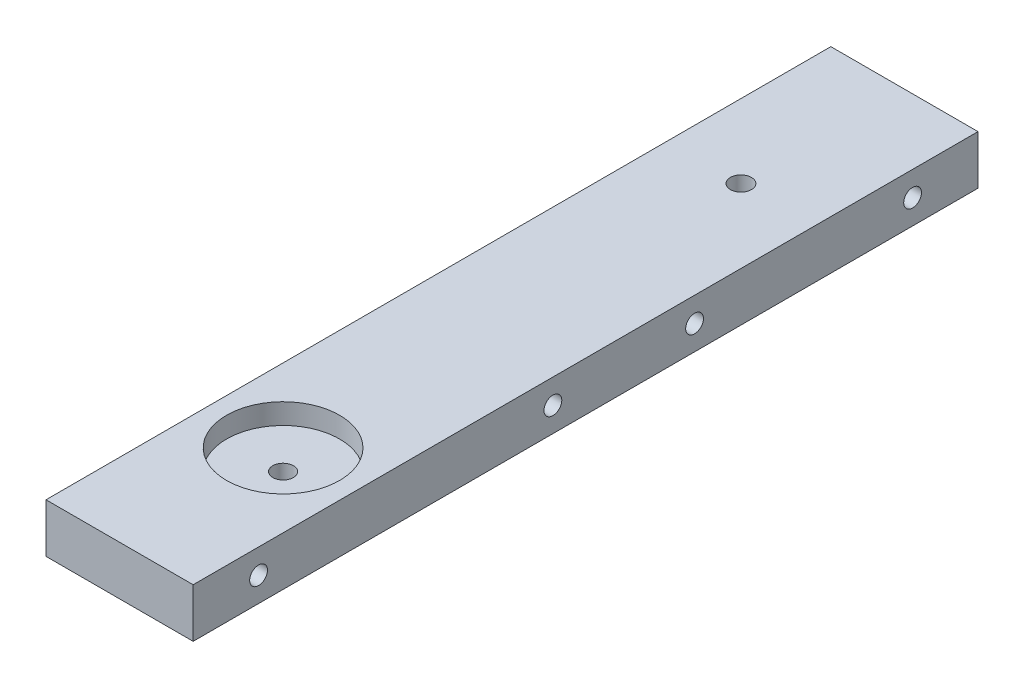
SolidWorks part; units mm, degrees
ref_plane "Front Plane" through (0, 0, 0) normal (0, 0, 1) x (1, 0, 0)
ref_plane "Top Plane" through (0, 0, 0) normal (0, 1, 0) x (1, 0, 0)
ref_plane "Right Plane" through (0, 0, 0) normal (1, 0, 0) x (0, 0, -1)
sketch "Sketch2" plane through (0, 0, 0) normal (0, 1, 0) x (1, 0, 0)
  line L0 (0, 0) -> (0, 152.4)
  line L1 (0, 152.4) -> (28.575, 152.4)
  line L2 (28.575, 152.4) -> (28.575, 0)
  line L3 (28.575, 0) -> (0, 0)
  dimension "D1" = 152.4
  dimension "D2" = 28.575
extrude "Boss-Extrude1" add sketch "Sketch2" along normal blind 9.525
sketch "Sketch3" plane through (0, 0, 0) normal (-1, 0, 0) x (0, 0, 1)
  line L3 (-152.4, 9.525) -> (0, 9.525) construction
  line L4 (-152.4, 9.525) -> (-152.4, 0) construction
  point P6 (-139.7, 4.7625)
  point P14 (-139.7, 4.7625)
  dimension "D1" = 4.7625
  dimension "D2" = 12.7
sketch "Sketch8" plane through (0, 0, 0) normal (-1, 0, 0) x (0, 0, 1)
  point P0 (-139.7, 4.7625)
hole_wizard "#5 Clearance Hole3" positions "Sketch8" profile "Sketch9" hole size "#5" standard "ANSI Inch" end condition through all
sketch "Sketch9" plane through (0, 4.7625, -139.7) normal (0, 1, 0) x (0, 0, 1)
  line L0 (0, 0) -> (0, 28.575)
  line L1 (0, 28.575) -> (1.7272, 28.575)
  line L2 (1.7272, 28.575) -> (1.7272, 0)
  line L5 (1.7272, 0) -> (0, 0)
  line L11 (0, -6.35) -> (0, 107.95) construction
  dimension "Thru Hole Dia." = 3.4544
  dimension "Thru Hole Depth" = 28.575
pattern_linear "LPattern1" count 4 spacing 42.3333 along (0, 0, 1) skipping (2, 0) of "#5 Clearance Hole3"
sketch "Sketch12" plane through (0, 9.525, 0) normal (0, 1, 0) x (1, 0, 0)
  line L0 (28.575, 0) -> (28.575, 152.4) construction
  line L2 (0, 0) -> (28.575, 0) construction
  circle A1 centre (14.2875, 31.75) radius 10.975
  circle A2 centre (14.2875, 120.65) radius 2.05
  point P0 (14.2875, 120.65)
  point P1 (14.2875, 76.2)
  point P2 (14.2875, 31.75)
  dimension "D8" = 4.1
  dimension "D9" = 21.95
  dimension "D1" = 14.2875
  dimension "D2" = 14.2875
  dimension "D3" = 14.2875
  dimension "D4" = 76.2
  dimension "D5" = 44.45
  dimension "D6" = 44.45
sketch "Sketch13" plane through (0, 0, 0) normal (-1, 0, 0) x (0, 0, 1)
  line L2 (0, 9.525) -> (0, 0) construction
  line L3 (-152.4, 9.525) -> (0, 9.525) construction
  point P5 (-69.85, 4.7625)
  dimension "D1" = 69.85
  dimension "D2" = 4.7625
hole_wizard "#5 Clearance Hole5" positions "Sketch13" profile "Sketch14" hole size "#5" standard "ANSI Inch" end condition through all
sketch "Sketch14" plane through (0, 4.7625, -69.85) normal (0, 1, 0) x (0, 0, 1)
  line L0 (0, 0) -> (0, 28.575)
  line L1 (0, 28.575) -> (1.7272, 28.575)
  line L2 (1.7272, 28.575) -> (1.7272, 0)
  line L5 (1.7272, 0) -> (0, 0)
  line L11 (0, -6.35) -> (0, 107.95) construction
  dimension "Thru Hole Dia." = 3.4544
  dimension "Thru Hole Depth" = 28.575
extrude "Cut-Extrude1" cut sketch "Sketch12" against normal through all contours A2
extrude "Cut-Extrude2" cut sketch "Sketch12<4>" against normal blind 4 contours A1
sketch "Sketch12<4>" plane through (0, 9.525, 0) normal (0, 1, 0) x (1, 0, 0) same geometry as "Sketch12"
sketch "Sketch15" plane through (0, 5.525, 0) normal (0, 1, 0) x (1, 0, 0)
  circle A0 centre (14.2875, 31.75) radius 2
  dimension "D1" = 4
extrude "Cut-Extrude3" cut sketch "Sketch15" against normal through all
